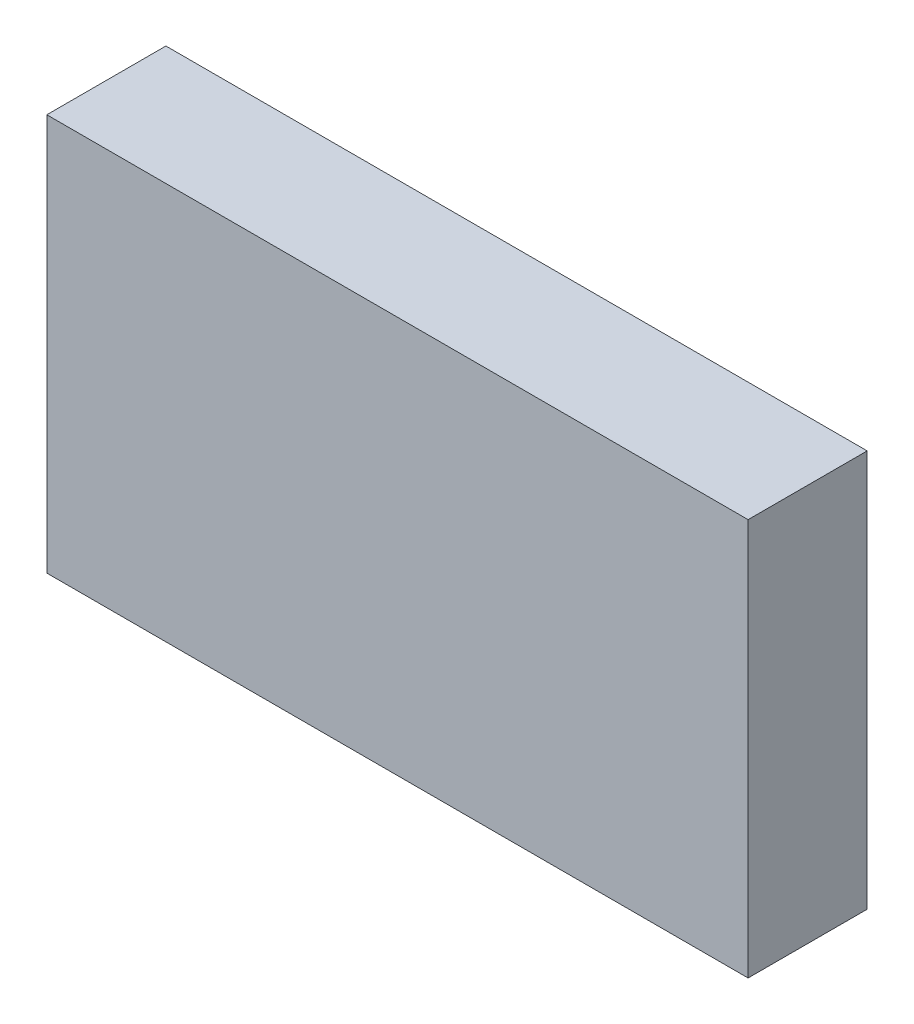
SolidWorks part; units mm, degrees
ref_plane "Ebene vorne" through (0, 0, 0) normal (0, 0, 1) x (1, 0, 0)
ref_plane "Ebene oben" through (0, 0, 0) normal (0, 1, 0) x (1, 0, 0)
ref_plane "Ebene rechts" through (0, 0, 0) normal (1, 0, 0) x (0, 0, -1)
sketch "Sketch1" plane through (0, 0, 0) normal (0, 0, 1) x (1, 0, 0)
  line L0 (0, 0) -> (0, 20.4208) construction
  line L1 (-26.5, 15) -> (26.5, 15)
  line L2 (-26.5, 15) -> (-26.5, -15)
  line L3 (-26.5, -15) -> (26.5, -15)
  line L4 (26.5, 15) -> (26.5, -15)
  line L5 (0, 0) -> (42.3663, 0) construction
  dimension "D1" = 53
  dimension "D2" = 30
extrude "Boss-Extrude1" add sketch "Sketch1" along normal blind 9
